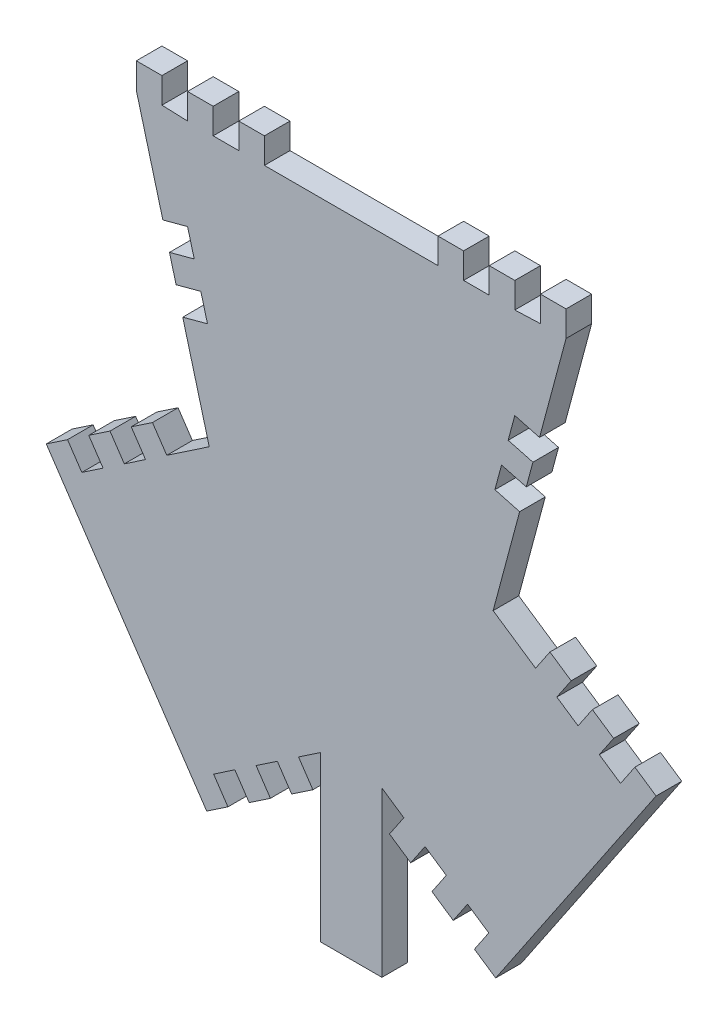
SolidWorks part; units mm, degrees
ref_plane "Plan de face" through (0, 0, 0) normal (0, 0, 1) x (1, 0, 0)
ref_plane "Plan de dessus" through (0, 0, 0) normal (0, 1, 0) x (1, 0, 0)
ref_plane "Plan de droite" through (0, 0, 0) normal (1, 0, 0) x (0, 0, -1)
sketch "Esquisse1" plane through (0, 0, 0) normal (0, 0, 1) x (1, 0, 0)
  line L2 (-88.0786, 23.9745) -> (-84.1963, 9.4857)
  line L3 (-88.0786, 23.9745) -> (-83.2488, 25.2682)
  line L4 (-84.5429, 30.0978) -> (-83.2488, 25.2682)
  line L5 (-89.3727, 28.8042) -> (-84.5429, 30.0978)
  line L6 (-89.3727, 28.8042) -> (-90.6668, 33.6338)
  line L7 (-90.6668, 33.6338) -> (-85.837, 34.9274)
  line L8 (-87.1307, 39.7572) -> (-85.837, 34.9274)
  line L9 (-91.9604, 38.4635) -> (-87.1307, 39.7572)
  line L10 (-91.9604, 38.4635) -> (-97.1368, 57.7821)
  line L12 (-84.1963, -32.2371) -> (-84.1963, 66.8937) construction
  line L13 (-55.1963, 76.5626) -> (-55.1963, -12.9651) construction
  line L16 (-26.1998, -32.4235) -> (-26.1998, 66.7073) construction
  line L18 (-18.4322, 38.4635) -> (-13.2558, 57.7821)
  line L19 (-18.4322, 38.4635) -> (-23.2619, 39.7572)
  line L20 (-23.2619, 39.7572) -> (-24.5556, 34.9274)
  line L21 (-19.7258, 33.6338) -> (-24.5556, 34.9274)
  line L22 (-21.0199, 28.8042) -> (-19.7258, 33.6338)
  line L23 (-21.0199, 28.8042) -> (-25.8497, 30.0978)
  line L24 (-25.8497, 30.0978) -> (-27.1437, 25.2682)
  line L25 (-22.314, 23.9745) -> (-27.1437, 25.2682)
  line L26 (-22.314, 23.9745) -> (-26.1963, 9.4857)
  line L29 (-97.1368, 57.7821) -> (-97.1368, 62.7821)
  line L30 (-97.1368, 62.7821) -> (-92.1368, 62.7821)
  line L31 (-92.1368, 62.7821) -> (-92.1368, 57.7821)
  line L32 (-92.1368, 57.7821) -> (-87.1403, 57.5957)
  line L33 (-87.1403, 57.5957) -> (-87.1403, 62.5957)
  line L34 (-87.1403, 62.5957) -> (-82.1403, 62.5957)
  line L35 (-82.1403, 62.5957) -> (-82.1403, 57.5957)
  line L36 (-82.1403, 57.5957) -> (-77.1403, 57.5957)
  line L37 (-77.1403, 57.5957) -> (-77.1403, 62.5957)
  line L38 (-77.1403, 62.5957) -> (-72.1403, 62.5957)
  line L39 (-72.1403, 62.5957) -> (-72.1403, 57.5957)
  line L40 (-72.1403, 57.5957) -> (-38.2523, 57.5957)
  line L41 (-38.2523, 62.5957) -> (-38.2523, 57.5957)
  line L42 (-33.2523, 62.5957) -> (-38.2523, 62.5957)
  line L43 (-33.2523, 57.5957) -> (-33.2523, 62.5957)
  line L44 (-28.2523, 57.5957) -> (-33.2523, 57.5957)
  line L45 (-28.2523, 62.5957) -> (-28.2523, 57.5957)
  line L46 (-23.2523, 62.5957) -> (-28.2523, 62.5957)
  line L47 (-23.2523, 57.5957) -> (-23.2523, 62.5957)
  line L48 (-18.2558, 57.7821) -> (-23.2523, 57.5957)
  line L49 (-18.2558, 62.7821) -> (-18.2558, 57.7821)
  line L50 (-13.2558, 62.7821) -> (-18.2558, 62.7821)
  line L51 (-13.2558, 57.7821) -> (-13.2558, 62.7821)
  line L52 (-92.1368, 57.7821) -> (-96.8019, 56.5321) construction
  line L54 (-61.1963, -36.1892) -> (-61.1963, -68.1892)
  line L56 (-114.7145, -10.7705) -> (-83.3997, -57.1966)
  line L62 (-84.1963, 9.4857) -> (-26.1963, 9.4857) construction
  line L63 (-114.7145, -10.7705) -> (-110.5693, -7.9746)
  line L64 (-110.5693, -7.9746) -> (-107.7733, -12.1198)
  line L65 (-107.7733, -12.1198) -> (-103.6281, -9.3238)
  line L66 (-103.6281, -9.3238) -> (-106.4241, -5.1786)
  line L67 (-106.4241, -5.1786) -> (-102.2789, -2.3826)
  line L68 (-102.2789, -2.3826) -> (-99.4829, -6.5278)
  line L69 (-99.4829, -6.5278) -> (-95.3378, -3.7319)
  line L70 (-95.3378, -3.7319) -> (-98.1337, 0.4133)
  line L71 (-98.1337, 0.4133) -> (-93.9885, 3.2093)
  line L72 (-93.9885, 3.2093) -> (-91.1926, -0.9359)
  line L73 (-91.1926, -0.9359) -> (-82.9022, 4.656)
  line L74 (-82.9022, 4.656) -> (-84.1963, 9.4857)
  line L75 (-99.0571, -33.9836) -> (-106.8362, -39.2307) construction
  line L76 (-62.6737, -43.2168) -> (-65.4697, -39.0716)
  line L77 (-66.8189, -46.0128) -> (-62.6737, -43.2168)
  line L78 (-69.6149, -41.8676) -> (-66.8189, -46.0128)
  line L79 (-73.7601, -44.6636) -> (-69.6149, -41.8676)
  line L80 (-70.9641, -48.8087) -> (-73.7601, -44.6636)
  line L81 (-75.1093, -51.6047) -> (-70.9641, -48.8087)
  line L82 (-77.9053, -47.4595) -> (-75.1093, -51.6047)
  line L83 (-82.0504, -50.2555) -> (-77.9053, -47.4595)
  line L84 (-79.2545, -54.4007) -> (-82.0504, -50.2555)
  line L85 (-83.3997, -57.1966) -> (-79.2545, -54.4007)
  line L87 (-61.1963, -36.1892) -> (-65.4697, -39.0716)
  line L88 (-11.3355, -33.9836) -> (-3.5563, -39.2307) construction
  line L89 (-61.1963, -68.1892) -> (-49.1963, -68.1892)
  line L90 (-26.1998, -32.4235) -> (-26.1998, 66.7073) construction
  line L91 (-49.1963, -36.1892) -> (-44.9229, -39.0716)
  line L92 (-31.1381, -54.4007) -> (-28.3421, -50.2555)
  line L93 (-28.3421, -50.2555) -> (-32.4873, -47.4595)
  line L94 (-32.4873, -47.4595) -> (-35.2833, -51.6047)
  line L95 (-35.2833, -51.6047) -> (-39.4285, -48.8087)
  line L96 (-39.4285, -48.8087) -> (-36.6325, -44.6636)
  line L97 (-36.6325, -44.6636) -> (-40.7777, -41.8676)
  line L98 (-40.7777, -41.8676) -> (-43.5737, -46.0128)
  line L99 (-43.5737, -46.0128) -> (-47.7188, -43.2168)
  line L100 (-47.7188, -43.2168) -> (-44.9229, -39.0716)
  line L101 (-19.2, -0.9359) -> (-27.4904, 4.656)
  line L102 (-16.404, 3.2093) -> (-19.2, -0.9359)
  line L103 (-12.2589, 0.4133) -> (-16.404, 3.2093)
  line L104 (-15.0548, -3.7319) -> (-12.2589, 0.4133)
  line L105 (-10.9096, -6.5278) -> (-15.0548, -3.7319)
  line L106 (-8.1137, -2.3826) -> (-10.9096, -6.5278)
  line L107 (-3.9685, -5.1786) -> (-8.1137, -2.3826)
  line L108 (-6.7644, -9.3238) -> (-3.9685, -5.1786)
  line L109 (-2.6193, -12.1198) -> (-6.7644, -9.3238)
  line L110 (0.1767, -7.9746) -> (-2.6193, -12.1198)
  line L111 (4.3219, -10.7705) -> (0.1767, -7.9746)
  line L112 (4.3219, -10.7705) -> (-26.9929, -57.1966)
  line L113 (-26.9929, -57.1966) -> (-31.1381, -54.4007)
  line L114 (-27.4904, 4.656) -> (-26.1963, 9.4857)
  line L115 (-49.1963, -68.1892) -> (-49.1963, -36.1892)
  point P23 (-55.1963, 57.5957)
  point P46 (-55.1963, 57.5957)
  point P84 (-55.1963, -38.2852)
  dimension "D1" = 5
  dimension "D2" = 15
  dimension "D3" = 46
  dimension "D4" = 5
  dimension "D5" = 5
  dimension "D6" = 50
  dimension "D7" = 29
  dimension "D8" = 5
  dimension "D9" = 20
  dimension "D10" = 18.7059
  dimension "D11" = 10
  dimension "D12" = 5
  dimension "D13" = 5
  dimension "D14" = 5
  dimension "D15" = 5
  dimension "D16" = 32
  dimension "D17" = 6
  dimension "D18" = 56
extrude "Boss.-Extru.1" add sketch "Esquisse1" along normal blind 5
